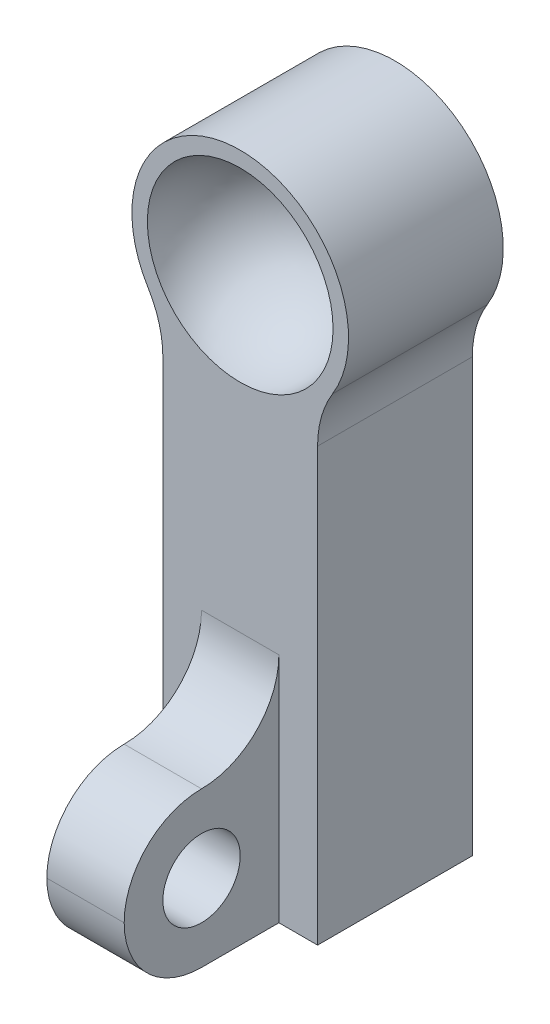
SolidWorks part; units mm, degrees
ref_plane "Ebene vorne" through (0, 0, 0) normal (0, 0, 1) x (1, 0, 0)
ref_plane "Ebene oben" through (0, 0, 0) normal (0, 1, 0) x (1, 0, 0)
ref_plane "Ebene rechts" through (0, 0, 0) normal (1, 0, 0) x (0, 0, -1)
sketch "Skizze1" plane through (0, 0, 0) normal (0, 0, 1) x (1, 0, 0)
  line L2 (-2.5, -3.5355) -> (-2.5, -17.5)
  line L3 (-2.5, -17.5) -> (2.5, -17.5)
  line L4 (2.5, -3.5355) -> (2.5, -17.5)
  arc A0 (2.9815, -1.8332) -> (-2.9815, -1.8332) centre (0, 0) ccw
  arc A1 (2.9815, -1.8332) -> (2.5, -3.5355) centre (5.75, -3.5355) ccw
  arc A2 (-2.5, -3.5355) -> (-2.9815, -1.8332) centre (-5.75, -3.5355) ccw
  dimension "D3" = 7
  dimension "D4" = 3.25
  dimension "D1" = 5
  dimension "D2" = 2.5
  dimension "D5" = 17.5
extrude "Aufsatz-Linear austragen1" add sketch "Skizze1" along normal blind 5
sketch "Skizze2" plane through (0, 0, 0) normal (1, 0, 0) x (0, 0, -1)
  line L1 (-5, -17.5) -> (-10, -17.5)
  line L2 (-5, -17.5) -> (-5, -12.5)
  line L3 (-5, -12.5) -> (-10, -12.5)
  line L4 (-10, -17.5) -> (-10, -12.5)
  dimension "D1" = 5
  dimension "D2" = 5
extrude "Aufsatz-Linear austragen2" add sketch "Skizze2" along normal blind 1.25 and the other way blind 1.25
sketch "Skizze3" plane through (1.25, 0, 0) normal (1, 0, 0) x (0, 0, -1)
  line L1 (-10, -12.5) -> (-10, -17.5) construction
  line L2 (-5, -12.5) -> (-10, -12.5) construction
  circle A0 centre (-7.5, -15) radius 1.25
  dimension "D1" = 2.5
  dimension "D2" = 2.5
  dimension "D3" = 2.5
extrude "Schnitt-Linear austragen1" cut sketch "Skizze3" against normal blind 3.25
sketch "Skizze4" plane through (0, 0, 0) normal (0, 1, 0) x (1, 0, 0)
  line L0 (7.7257, -5) -> (-7.4435, -5) construction
  line L1 (-3.5, -5) -> (3.5, -5) construction
  line L2 (3, -5) -> (-3, -5)
  arc A0 (3, -5) -> (-3, -5) centre (0, -5) ccw
  dimension "D1" = 6
  dimension "D2" = 0
revolve "Schnitt-Rotation1" cut sketch "Skizze4" angle 360 about L0
hole_wizard "M3 Gewindebohrung1" positions "3D-Skizze1" profile "Skizze5" tap size "M3" standard "DIN"
sketch3d "3D-Skizze1"
  line L0 (-2.5, -17.5, 5) -> (-2.5, -17.5, 0) construction
  line L1 (-2.5, -17.5, 0) -> (2.5, -17.5, 0) construction
  point P0 (0, -17.5, 2.5)
  dimension "D1" = 2.5
  dimension "D2" = 2.5
sketch "Skizze5" plane through (0, -17.5, 2.5) normal (1, 0, 0) x (0, 0, -1)
  line L0 (0, 0) -> (0, 9.2511)
  line L1 (0, 9.2511) -> (1.25, 8.5)
  line L2 (1.25, 8.5) -> (1.25, 0)
  line L5 (1.25, 0) -> (0, 0)
  line L10 (0, 9.2511) -> (-1.25, 8.5) construction
  line L11 (0, -6.35) -> (0, 107.95) construction
  dimension "Bohrerdurchmesser" = 2.5
  dimension "Bohrungstiefe" = 8.5
  dimension "Spitzenwinkel" = 118
cosmetic thread "Bohrungsgewinde1" parameters "D1"=6, "D2"=3
fillet "Verrundung1" radius 2.5 3 edges at (0, -12.5, 5) (0, -12.5, 10) (0, -17.5, 10)
